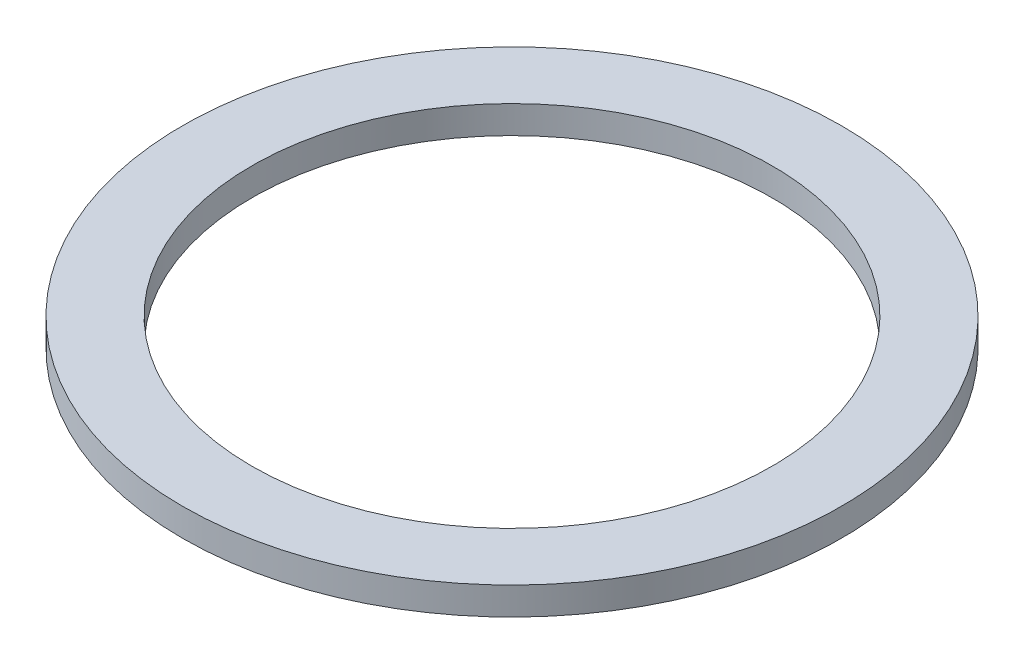
SolidWorks part; units mm, degrees
ref_plane "Front Plane" through (0, 0, 0) normal (0, 0, 1) x (1, 0, 0)
ref_plane "Top Plane" through (0, 0, 0) normal (0, 1, 0) x (1, 0, 0)
ref_plane "Right Plane" through (0, 0, 0) normal (1, 0, 0) x (0, 0, -1)
sketch "Sketch1" plane through (0, 0, 0) normal (0, 1, 0) x (1, 0, 0)
  circle A0 centre (0, 0) radius 47.5
  dimension "FLANGE_OD" = 95
extrude "Boss-Extrude1" add sketch "Sketch1" along normal blind 4
sketch "Sketch2" plane through (0, 0, 0) normal (0, 1, 0) x (1, 0, 0)
  circle A0 centre (0, 0) radius 37.5
  dimension "BORE_D" = 75
extrude "Cut-Extrude1" cut sketch "Sketch2" along normal through all
sketch "Sketch3" plane through (0, 4, 0) normal (0, 1, 0) x (1, 0, 0)
  circle A0 centre (0, 0) radius 20.7138 construction
  circle A1 centre (-20.7138, 0) radius 1.5839
  dimension "BOLT_D" = 3.1679
  dimension "BOLT_PCD" = 41.4276
extrude "Cut-Extrude2" cut sketch "Sketch3" against normal blind 3.9068 rebuild error yes
pattern_circular "CirPattern1" count 6 over 360 rebuild error yes
